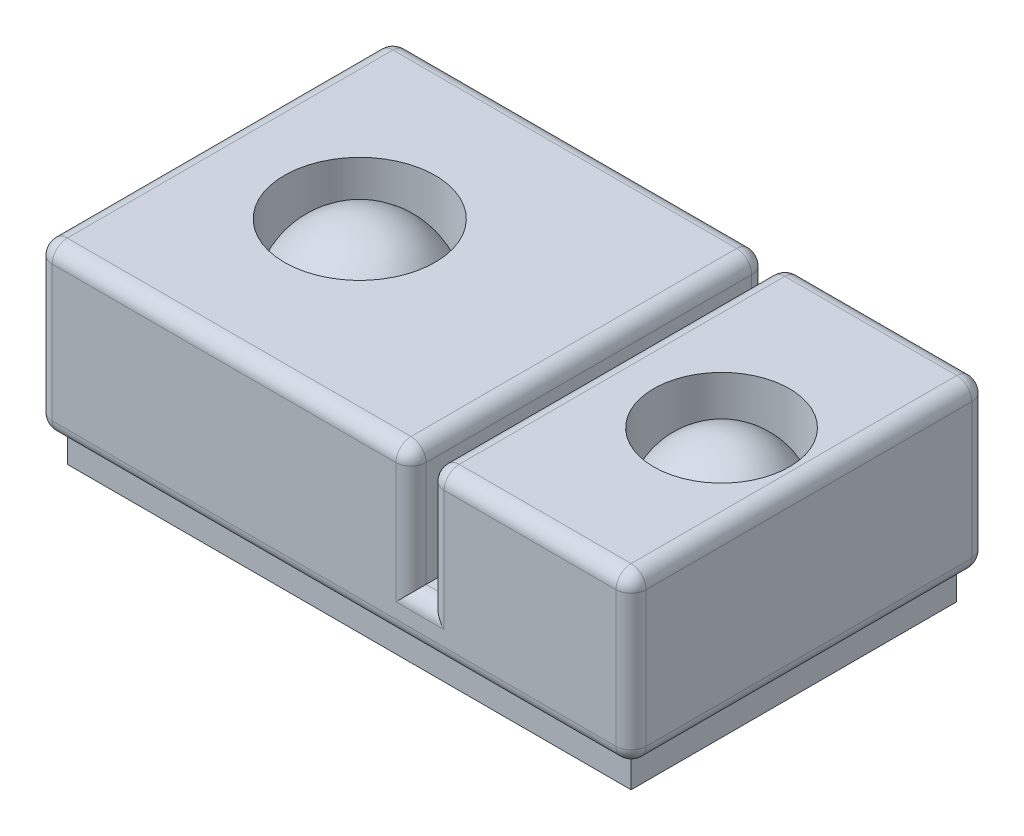
SolidWorks part; units mm, degrees
ref_plane "Front Plane" through (0, 0, 0) normal (0, 0, 1) x (1, 0, 0)
ref_plane "Top Plane" through (0, 0, 0) normal (0, 1, 0) x (1, 0, 0)
ref_plane "Right Plane" through (0, 0, 0) normal (1, 0, 0) x (0, 0, -1)
sketch "草图1" plane through (0, 0, 0) normal (0, 1, 0) x (1, 0, 0)
  line L1 (-1.97, -1.18) -> (1.97, -1.18)
  line L2 (-1.97, -1.18) -> (-1.97, 1.18)
  line L3 (-1.97, 1.18) -> (1.97, 1.18)
  line L4 (1.97, -1.18) -> (1.97, 1.18)
  line L5 (-1.97, -1.18) -> (1.97, 1.18) construction
  line L6 (-1.97, 1.18) -> (1.97, -1.18) construction
  point P0 (0, 0)
  dimension "D1" = 3.94
  dimension "D2" = 2.36
extrude "Boss-Extrude1" add sketch "草图1" along normal blind 1.1
sketch "草图2" plane through (0, 0, 0) normal (0, -1, 0) x (1, 0, 0)
  line L0 (-1.97, 1.18) -> (1.97, 1.18) construction
  line L1 (-1.87, 1.08) -> (1.87, 1.08)
  line L2 (-1.87, 1.08) -> (-1.87, -1.08)
  line L3 (-1.87, -1.08) -> (1.87, -1.08)
  line L4 (1.87, 1.08) -> (1.87, -1.08)
  line L5 (-1.87, 1.08) -> (1.87, -1.08) construction
  line L6 (-1.87, -1.08) -> (1.87, 1.08) construction
  line L7 (1.97, 1.18) -> (1.97, -1.18) construction
  point P0 (0, 0)
  dimension "D1" = 0.1
  dimension "D2" = 0.1
extrude "Boss-Extrude2" add sketch "草图2" along normal blind 0.2
sketch "草图3" plane through (0, -0.2, 0) normal (0, -1, 0) x (1, 0, 0)
  line L0 (-2.1982, 0) -> (2.1826, 0) construction
  line L1 (0, 1.3856) -> (0, -1.4207) construction
  line L2 (-1.87, 1.08) -> (-1.87, -1.08) construction
  line L3 (-1.82, 1.03) -> (-1.1, 1.03)
  line L4 (-1.82, 1.03) -> (-1.82, 0.43)
  line L5 (-1.82, 0.43) -> (-1.1, 0.43)
  line L6 (-1.1, 1.03) -> (-1.1, 0.43)
  line L7 (-1.82, 1.03) -> (-1.1, 0.43) construction
  line L8 (-1.82, 0.43) -> (-1.1, 1.03) construction
  line L9 (1.87, 1.08) -> (-1.87, 1.08) construction
  line L10 (-0.13, 1.03) -> (-0.13, 0.43)
  line L11 (-0.85, 0.43) -> (-0.13, 0.43)
  line L12 (-0.85, 1.03) -> (-0.85, 0.43)
  line L13 (-0.85, 1.03) -> (-0.13, 1.03)
  line L14 (0.84, 1.03) -> (0.84, 0.43)
  line L15 (0.12, 0.43) -> (0.84, 0.43)
  line L16 (0.12, 1.03) -> (0.12, 0.43)
  line L17 (0.12, 1.03) -> (0.84, 1.03)
  line L18 (1.81, 1.03) -> (1.81, 0.43)
  line L19 (1.09, 0.43) -> (1.81, 0.43)
  line L20 (1.09, 1.03) -> (1.09, 0.43)
  line L21 (1.09, 1.03) -> (1.81, 1.03)
  line L22 (-0.13, -0.42) -> (-0.13, -1.02)
  line L23 (-0.85, -1.02) -> (-0.13, -1.02)
  line L24 (-0.85, -0.42) -> (-0.85, -1.02)
  line L25 (-0.85, -0.42) -> (-0.13, -0.42)
  line L26 (0.84, -0.42) -> (0.84, -1.02)
  line L27 (0.12, -1.02) -> (0.84, -1.02)
  line L28 (0.12, -0.42) -> (0.12, -1.02)
  line L29 (0.12, -0.42) -> (0.84, -0.42)
  line L30 (1.81, -0.42) -> (1.81, -1.02)
  line L31 (1.09, -1.02) -> (1.81, -1.02)
  line L32 (1.09, -0.42) -> (1.09, -1.02)
  line L33 (1.09, -0.42) -> (1.81, -0.42)
  line L34 (-1.1, -0.42) -> (-1.1, -1.02)
  line L35 (-1.82, -1.02) -> (-1.1, -1.02)
  line L36 (-1.82, -0.42) -> (-1.82, -1.02)
  line L37 (-1.82, -0.42) -> (-1.1, -0.42)
  point P5 (-1.46, 0.73)
  dimension "D1" = 0.6
  dimension "D2" = 0.72
  dimension "D3" = 0.05
  dimension "D4" = 0.05
  dimension "D5" = 4
  dimension "D6" = 2
extrude "Boss-Extrude3" add sketch "草图3" along normal blind 0.05
sketch "草图4" plane through (0, 1.1, 0) normal (0, 1, 0) x (1, 0, 0)
  line L0 (-1.97, -1.18) -> (1.97, -1.18) construction
  line L1 (0.63, -1.18) -> (0.51, -1.18)
  line L2 (0.63, -1.18) -> (0.63, 1.18)
  line L3 (0.63, 1.18) -> (0.51, 1.18)
  line L4 (0.51, -1.18) -> (0.51, 1.18)
  line L5 (1.97, 1.18) -> (-1.97, 1.18) construction
  line L7 (1.97, -1.18) -> (1.97, 1.18) construction
  dimension "D1" = 1.34
  dimension "D2" = 0.12
extrude "Cut-Extrude1" cut sketch "草图4" against normal blind 0.8
fillet "Fillet1" radius 0.1 22 edges at (-1.97, 0, 0) (0.51, 0.7, -1.18) (-1.97, 0.55, -1.18) (0, 0, -1.18) (0.63, 0.7, -1.18) (0.57, 0.3, -1.18) (1.97, 0.55, -1.18) (1.97, 0, 0) (1.97, 0.55, 1.18) (0, 0, 1.18) (-1.97, 0.55, 1.18) (0.51, 0.7, 1.18) (0.57, 0.3, 1.18) (0.63, 0.7, 1.18) (1.97, 1.1, 0) (1.3, 1.1, 1.18) (0.63, 1.1, 0) (1.3, 1.1, -1.18) (-1.97, 1.1, 0) (-0.73, 1.1, -1.18) (0.51, 1.1, 0) (-0.73, 1.1, 1.18)
sketch "草图5" plane through (0, 1.1, 0) normal (0, 1, 0) x (1, 0, 0)
  line L0 (1.97, 1.08) -> (1.97, -1.08) construction
  circle A0 centre (-1.01, 0) radius 0.5
  circle A1 centre (1.39, 0) radius 0.45
  dimension "D1" = 0.9
  dimension "D2" = 1
  dimension "D3" = 0.58
  dimension "D4" = 2.98
extrude "Cut-Extrude2" cut sketch "草图5" against normal blind 0.5
sketch "草图6" plane through (0, 0, 0) normal (0, 0, 1) x (1, 0, 0)
  line L0 (-0.51, 0.6) -> (-1.51, 0.6) construction
  line L2 (-1.51, 0.6) -> (-0.51, 0.6)
  line L4 (-1.01, 0.436) -> (-1.01, 1.3553) construction
  arc A0 (-0.51, 0.6) -> (-1.51, 0.6) centre (-1.01, 0.6) ccw
revolve "Boss-Revole1" add sketch "草图6" angle 360 about L4 region at (-1.2222, 0.8122, 0)
sketch "草图7" plane through (0, 0, 0) normal (0, 0, 1) x (1, 0, 0)
  line L0 (1.84, 0.6) -> (0.94, 0.6) construction
  line L1 (1.39, 0.6) -> (1.39, 1.2548) construction
  line L2 (0.94, 0.6) -> (1.39, 0.6)
  line L3 (1.39, 0.6) -> (1.39, 1.05)
  arc A0 (1.39, 1.05) -> (0.94, 0.6) centre (1.39, 0.6) ccw
revolve "Boss-Revole2" add sketch "草图7" angle 360 about L1
